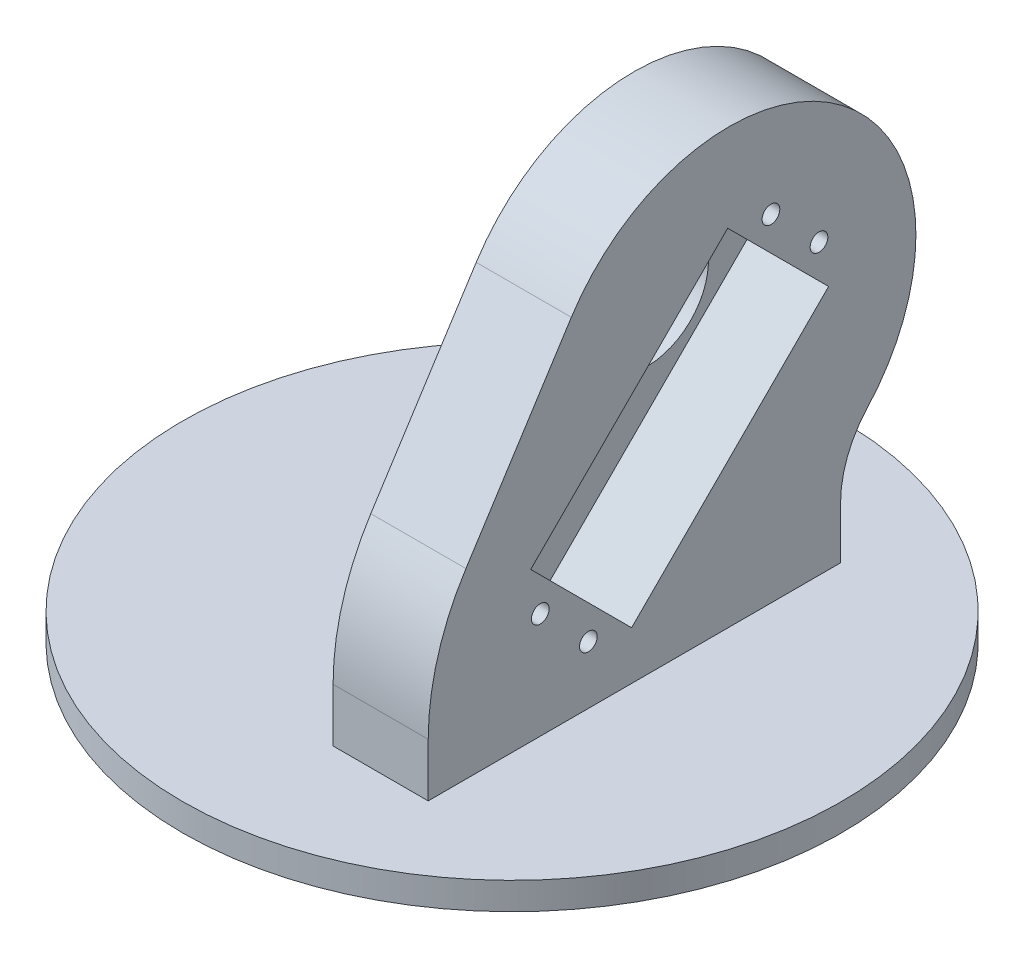
SolidWorks part; units mm, degrees
ref_plane "Front Plane" through (0, 0, 0) normal (0, 0, 1) x (1, 0, 0)
ref_plane "Top Plane" through (0, 0, 0) normal (0, 1, 0) x (1, 0, 0)
ref_plane "Right Plane" through (0, 0, 0) normal (1, 0, 0) x (0, 0, -1)
sketch "Sketch1" plane through (0, 0, 0) normal (0, 1, 0) x (1, 0, 0)
  line L0 (0, -7.25) -> (0, 7.25) construction
  circle A0 centre (0, 0) radius 48.5
  circle A1 centre (0, -7.25) radius 1.5
  circle A2 centre (0, 7.25) radius 1.5
  point P6 (0, 0)
  dimension "D2" = 97
  dimension "D3" = 3
  dimension "D1" = 14.5
extrude "Boss-Extrude1" add sketch "Sketch1" along normal blind 4
sketch "Sketch2" plane through (0, 4, 0) normal (0, 1, 0) x (1, 0, 0)
  circle A0 centre (0, 0) radius 3.75
  dimension "D1" = 7.5
extrude "Cut-Extrude1" cut sketch "Sketch2" against normal blind 1.5
sketch "Sketch3" plane through (0, 0, 0) normal (1, 0, 0) x (0, 0, -1)
  line L0 (30.34, 4) -> (-30.34, 4)
  line L1 (48.5, 4) -> (-48.5, 4) construction
  line L2 (30.34, 4) -> (30.34, 11.64)
  line L3 (30.34, 11.64) -> (45.34, 11.64) construction
  line L4 (3.75, 4) -> (-3.75, 4) construction
  line L5 (-30.34, 4) -> (-30.34, 11.86)
  line L6 (-24.7927, 30.8361) -> (-9.2781, 55.1041)
  arc A0 (30.34, 11.64) -> (34.2527, 21.7431) centre (45.34, 11.64) cw
  arc A1 (34.2527, 21.7431) -> (-9.2781, 55.1041) centre (13.91, 40.28) ccw
  arc A2 (-30.34, 11.86) -> (-24.7927, 30.8361) centre (4.89, 11.86) cw
  circle A3 centre (13.91, 40.28) radius 9
  point P5 (0, 4)
  point P17 (0, 0)
  point P18 (0, 0)
  point P19 (10.4174, 20.7112)
  point P20 (0, 0)
  dimension "D2" = 15
  dimension "D5" = 35.23
  dimension "D6" = 18
  dimension "D1" = 60.68
  dimension "D3" = 7.64
  dimension "D4" = 7.86
  dimension "D7" = 40.28
  dimension "D8" = 13.91
extrude "Boss-Extrude2" add sketch "Sketch3" along normal blind 14 from offset 4
sketch "Sketch5" plane through (0, 0, 0) normal (1, 0, 0) x (0, 0, -1)
  line L0 (-15.2592, 25.9592) -> (-0.41, 11.11)
  line L1 (-15.2592, 25.9592) -> (13.7321, 54.9506)
  line L2 (-0.41, 11.11) -> (28.5814, 40.1014)
  line L3 (13.7321, 54.9506) -> (28.5814, 40.1014)
  line L4 (-0.7636, 40.4549) -> (14.0857, 25.6057) construction
  line L5 (6.6611, 33.0303) -> (23.6316, 50.0009) construction
  line L6 (-30.34, 4) -> (30.34, 4) construction
  line L7 (20.0961, 53.5364) -> (27.1672, 46.4653) construction
  circle A0 centre (20.0961, 53.5364) radius 1.3
  circle A1 centre (27.1672, 46.4653) radius 1.3
  circle A2 centre (-6.774, 12.5242) radius 1.3
  circle A3 centre (-13.845, 19.5953) radius 1.3
  point P14 (23.6316, 50.0009)
  dimension "D8" = 2.6
  dimension "D1" = 11.11
  dimension "D2" = 0.41
  dimension "D3" = 21
  dimension "D4" = 41
  dimension "D5" = 45
  dimension "D6" = 3.5
  dimension "D7" = 10
extrude "Cut-Extrude2" cut sketch "Sketch5" along normal through all from offset 6
